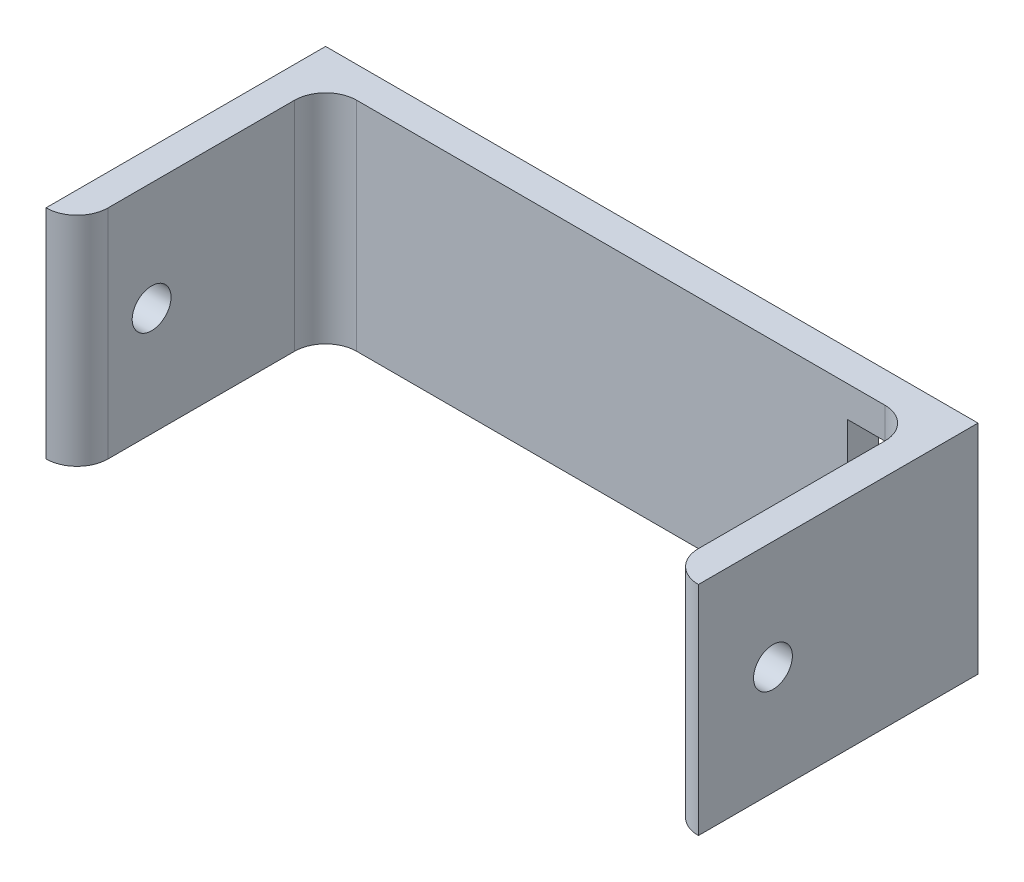
SolidWorks part; units mm, degrees
material "PE High Density"
ref_plane "Front Plane" through (0, 0, 0) normal (0, 0, 1) x (1, 0, 0)
ref_plane "Top Plane" through (0, 0, 0) normal (0, 1, 0) x (1, 0, 0)
ref_plane "Right Plane" through (0, 0, 0) normal (1, 0, 0) x (0, 0, -1)
sketch "Sketch1" plane through (0, 0, 0) normal (0, 1, 0) x (1, 0, 0)
  line L0 (0, 0) -> (0, 57.15)
  line L1 (0, 57.15) -> (133.35, 57.15)
  line L2 (133.35, 57.15) -> (133.35, 0)
  line L3 (133.35, 0) -> (127, 0)
  line L4 (127, 0) -> (127, 50.8)
  line L5 (127, 50.8) -> (6.35, 50.8)
  line L6 (6.35, 50.8) -> (6.35, 0)
  line L7 (6.35, 0) -> (0, 0)
  point P9 (3.175, 0)
  dimension "D1" = 6.35
  dimension "D2" = 6.35
  dimension "D3" = 133.35
  dimension "D4" = 57.15
  dimension "D5" = 6.35
extrude "Boss-Extrude1" add sketch "Sketch1" along normal blind 44.45 contours L7 L0 L1 L2 L3 L4 L5 L6
fillet "Fillet1" radius 6.35 2 edges at (127, 22.225, -50.8) (6.35, 22.225, -50.8)
fillet "Fillet2" radius 6.35 6 edges at (3.175, 0, 0) (127, 22.225, 0) (6.35, 22.225, 0) (130.175, 44.45, 0) (3.175, 44.45, 0) (130.175, 0, 0)
extrude "Cut-Extrude2" cut sketch "Sketch4" against normal blind 254
sketch "Sketch4" plane through (139.7, 1.4152, -69.9488) normal (1, 0, 0) x (0, 0, -1)
  circle A0 centre (-54.7088, 20.8098) radius 3.9687
sketch "Sketch5" plane through (0, 0, -50.8) normal (0, 0, 1) x (1, 0, 0)
  line L0 (120.65, 44.45) -> (12.7, 44.45) construction
  line L1 (113.03, 38.1) -> (124.46, 38.1)
  line L2 (113.03, 38.1) -> (113.03, 6.35)
  line L3 (113.03, 6.35) -> (124.46, 6.35)
  line L4 (124.46, 38.1) -> (124.46, 6.35)
  line L5 (127, 44.45) -> (127, 0) construction
  dimension "D1" = 31.75
  dimension "D2" = 6.35
  dimension "D3" = 13.97
  dimension "D4" = 11.43
extrude "Cut-Extrude4" cut sketch "Sketch5" against normal through all and the other way through all
